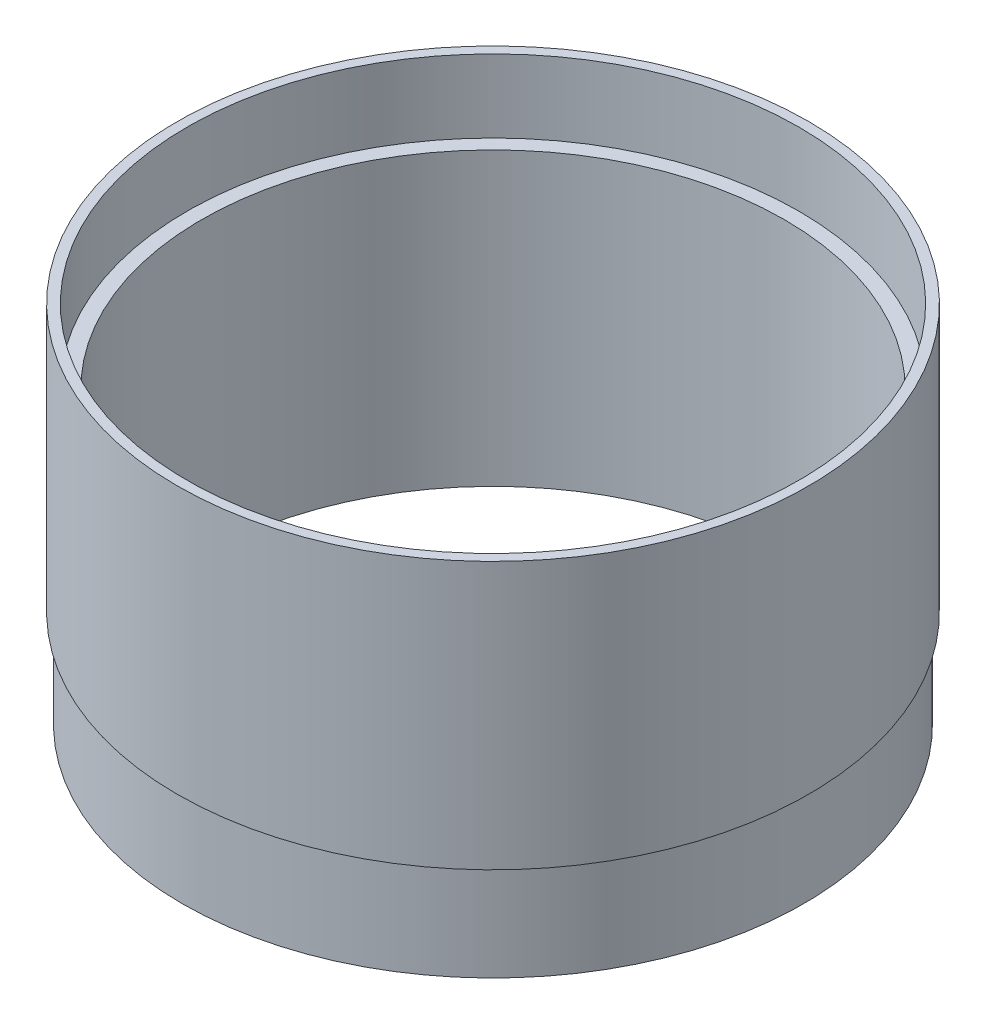
SolidWorks part; units mm, degrees
material "HYPALON"
ref_plane "Płaszczyzna przednia" through (0, 0, 0) normal (0, 0, 1) x (1, 0, 0)
ref_plane "Płaszczyzna górna" through (0, 0, 0) normal (0, 1, 0) x (1, 0, 0)
ref_plane "Płaszczyzna prawa" through (0, 0, 0) normal (1, 0, 0) x (0, 0, -1)
sketch "Szkic1" plane through (0, 0, 0) normal (0, 0, 1) x (1, 0, 0)
  line L0 (60, -30) -> (64, -30)
  line L1 (64, -30) -> (64, -10)
  line L3 (65, -10) -> (65, 45)
  line L4 (65, 45) -> (63, 45)
  line L5 (63, 45) -> (63, 30)
  line L6 (63, 30) -> (60, 30)
  line L7 (60, 30) -> (60, -30)
  line L8 (0, -40.0391) -> (0, 54.8743) construction
  line L9 (64, -10) -> (65, -10)
  point P4 (60, 0)
  dimension "D1" = 60
  dimension "D2" = 5
  dimension "D3" = 60
  dimension "D4" = 20
  dimension "D5" = 15
  dimension "D6" = 4
  dimension "D7" = 2
revolve "Obrót1" add sketch "Szkic1" angle 360 about L8
